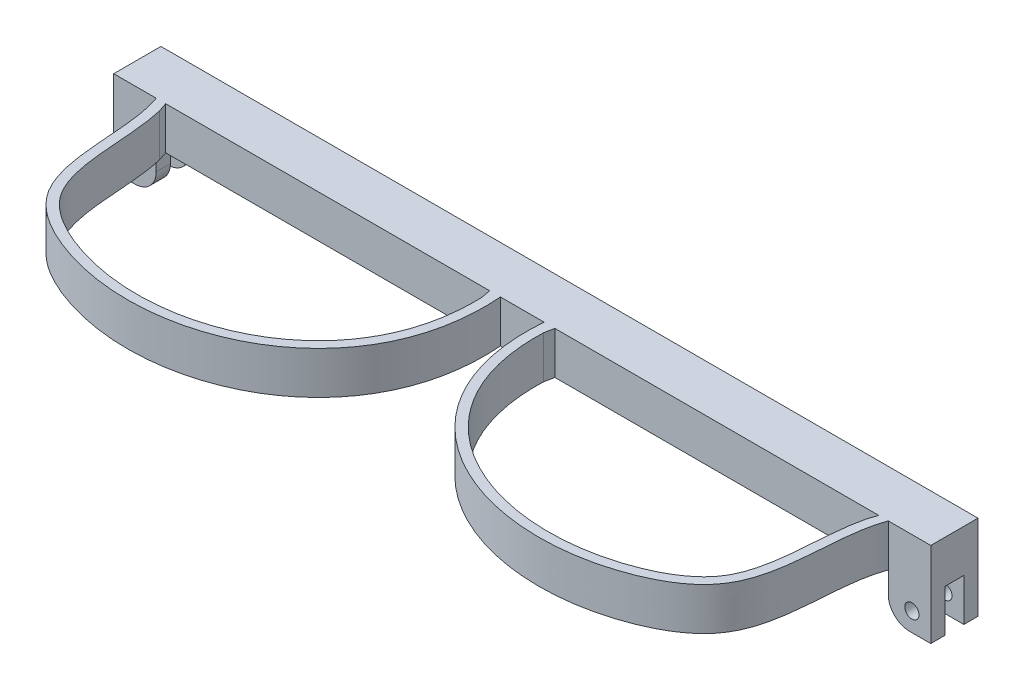
SolidWorks part; units mm, degrees
ref_plane "前视基准面" through (0, 0, 0) normal (0, 0, 1) x (1, 0, 0)
ref_plane "上视基准面" through (0, 0, 0) normal (0, 1, 0) x (1, 0, 0)
ref_plane "右视基准面" through (0, 0, 0) normal (1, 0, 0) x (0, 0, -1)
sketch "草图1" plane through (0, 0, 0) normal (0, 1, 0) x (1, 0, 0)
  line L0 (-85, 29.8187) -> (85, 29.8187)
  line L1 (85, 29.8187) -> (85, -30.1813)
  line L2 (85, -30.1813) -> (-85, -30.1813)
  line L3 (-85, -30.1813) -> (-85, 29.8187)
  line L4 (-77.5, 21.6616) -> (77.5, 21.6616)
  line L5 (-77.5, 21.6616) -> (-77.5, 11.6616)
  line L6 (-77.5, 11.6616) -> (-4.6224, 11.6616)
  line L8 (-74.8263, 9.6616) -> (-6.5113, 9.6616) construction
  line L10 (-4.6224, 11.6616) -> (4.6224, 11.6616)
  line L11 (0, 29.8187) -> (0, -30.1813) construction
  line L12 (77.5, 11.6616) -> (4.6224, 11.6616)
  line L13 (77.5, 21.6616) -> (77.5, 11.6616)
  spline S0 degree 3 poles (-77.5, 11.6616) (-74.4077, 3.1869) (-78.1308, -15.9273) (-40.2589, -37.426) (-2.1163, -20.689) (-4.6224, 11.6616) knots 0 0 0 0 0.246122 0.369792 1 1 1 1
  spline S1 degree 1 poles (-74.8263, 9.6616) (-6.5113, 9.6616) knots 0 0 1 1 construction
  spline S2 degree 3 poles (-74.8263, 9.6616) (-74.5371, 8.4402) (-74.1186, 5.9785) (-73.6218, 0.8691) (-73.2546, -5.557) (-72.241, -11.3706) (-70.6014, -15.2078) (-68.2701, -18.4305) (-63.7315, -21.7629) (-56.8543, -24.5334) (-49.7226, -26.1197) (-40.0582, -26.6566) (-30.6361, -24.878) (-22.3142, -20.9083) (-16.8289, -16.8747) (-12.2912, -11.8166) (-9.4499, -6.76) (-7.8343, -2.2025) (-6.9771, 1.4731) (-6.5812, 4.7599) (-6.4697, 7.5102) (-6.4856, 8.9503) (-6.5113, 9.6616) knots 0.022831 0.022831 0.022831 0.022831 0.052972 0.083113 0.143395 0.203676 0.233817 0.263958 0.324239 0.384521 0.444802 0.505084 0.625647 0.685929 0.74621 0.806492 0.866773 0.896914 0.927055 0.957196 0.972266 0.987337 0.987337 0.987337 0.987337
  spline S3 degree 1 poles (-74.8263, 9.6616) (-75.4985, 11.6616) knots 0 0 1 1
  spline S4 degree 1 poles (-6.5113, 9.6616) (-6.9074, 11.6616) knots 0 0 1 1
  spline S5 degree 1 poles (74.8263, 9.6616) (75.4985, 11.6616) knots 0 0 1 1
  spline S6 degree 1 poles (6.5113, 9.6616) (6.9074, 11.6616) knots 0 0 1 1
  spline S7 degree 3 poles (74.8263, 9.6616) (74.5371, 8.4402) (74.1186, 5.9785) (73.6218, 0.8691) (73.2546, -5.557) (72.241, -11.3706) (70.6014, -15.2078) (68.2701, -18.4305) (63.7315, -21.7629) (56.8543, -24.5334) (49.7226, -26.1197) (40.0582, -26.6566) (30.6361, -24.878) (22.3142, -20.9083) (16.8289, -16.8747) (12.2912, -11.8166) (9.4499, -6.76) (7.8343, -2.2025) (6.9771, 1.4731) (6.5812, 4.7599) (6.4697, 7.5102) (6.4856, 8.9503) (6.5113, 9.6616) knots 0.022831 0.022831 0.022831 0.022831 0.052972 0.083113 0.143395 0.203676 0.233817 0.263958 0.324239 0.384521 0.444802 0.505084 0.625647 0.685929 0.74621 0.806492 0.866773 0.896914 0.927055 0.957196 0.972266 0.987337 0.987337 0.987337 0.987337
  spline S8 degree 3 poles (77.5, 11.6616) (74.4077, 3.1869) (78.1308, -15.9273) (40.2589, -37.426) (2.1163, -20.689) (4.6224, 11.6616) knots 0 0 0 0 0.246122 0.369792 1 1 1 1
  point P3 (0, 29.8187)
  point P25 (0, 11.6616)
  point P31 (0, 21.6616)
  dimension "D1" = 60
  dimension "D2" = 170
  dimension "D3" = 10
  dimension "D4" = 77.5
  dimension "D5" = 2
extrude "frame_前端" add sketch "草图1" along normal blind 9 contours L13 L4 L5 L6 L10 L12 | S8 L12 S5 S7 S6 | S4 S2 S3 L6 S0 region at (0, 0, -16.6616) region at (-76.4992, 0, -10.8291) region at (42.3457, 0, 27.4934)
sketch "frame前端线槽草图" plane through (77.5, 0, 0) normal (1, 0, 0) x (0, 0, -1)
  line L0 (11.6616, 9) -> (11.6616, 0)
  line L2 (21.6616, 0) -> (21.6616, 9)
  line L3 (21.6616, 9) -> (11.6616, 9)
  line L4 (11.6616, 9) -> (21.6616, 0) construction
  line L5 (11.6616, 0) -> (21.6616, 9) construction
  line L6 (11.6616, 0) -> (13.6616, 0)
  line L7 (13.6616, 0) -> (13.6616, 7.2)
  line L8 (13.6616, 7.2) -> (19.6616, 7.2)
  line L9 (19.6616, 7.2) -> (19.6616, 0)
  line L10 (19.6616, 0) -> (21.6616, 0)
  line L11 (13.6616, 0) -> (19.6616, 0)
  line L12 (11.6616, 9) -> (11.6616, 0)
  line L13 (13.6616, 0) -> (13.6616, 7.2)
  line L14 (19.6616, 7.2) -> (19.6616, 0)
  line L15 (21.6616, 0) -> (21.6616, 9)
  point P4 (16.6616, 4.5)
  point P24 (16.6616, 4.5)
  dimension "D1" = 2
ref_plane "左侧connection草图生成面" through (0, 0, -16.6616) normal (0, 0, -1) x (-1, 0, 0)
ref_plane "向中间生成connection基底的基准面左" through (86.5, 0, 0) normal (1, 0, 0) x (0, 0, -1)
sketch "草图5" plane through (86.5, 0, 0) normal (1, 0, 0) x (0, 0, -1)
  line L0 (11.6616, 9) -> (11.6616, 0)
  line L1 (11.6616, 0) -> (21.6616, 0)
  line L2 (21.6616, 0) -> (21.6616, 9)
  line L3 (21.6616, 9) -> (11.6616, 9)
extrude "向中间生成connection的基底左" add sketch "草图5" against normal blind 9
sketch "草图9" plane through (0, 0, -16.6616) normal (0, 0, -1) x (-1, 0, 0)
  line L1 (-86.5, 4.95) -> (-86.5, -4.95) construction
  line L4 (-86.5, 0) -> (-86.5, -9)
  line L5 (-86.5, -9) -> (-82, -9)
  line L7 (-86.5, 0) -> (-77.5, 0)
  line L8 (77.5, 0) -> (-86.5, 0) construction
  line L9 (-77.5, 0) -> (-77.5, -4.5)
  arc A2 (-82, -9) -> (-77.5, -4.5) centre (-82, -4.5) ccw
  dimension "D4" = 9
  dimension "D1" = 9
  dimension "D2" = 4.5
  dimension "D3" = 4.5
extrude "生成connection左上" add sketch "草图9" along normal blind 5
extrude "生成connection左下" add sketch "草图9<3>" against normal blind 5
sketch "草图9<3>" plane through (0, 0, -16.6616) normal (0, 0, -1) x (-1, 0, 0) same geometry as "草图9"
extrude "生成connection口左上" cut sketch "草图9<4>" against normal blind 2
sketch "草图9<4>" plane through (0, 0, -16.6616) normal (0, 0, -1) x (-1, 0, 0) same geometry as "草图9"
extrude "生成connection口左下" cut sketch "草图9<6>" along normal blind 2
sketch "草图9<6>" plane through (0, 0, -16.6616) normal (0, 0, -1) x (-1, 0, 0) same geometry as "草图9"
ref_plane "线槽口草图基准面" through (77.5, 0, 0) normal (1, 0, 0) x (0, 0, -1)
sketch "线槽口草图" plane through (77.5, 0, 0) normal (1, 0, 0) x (0, 0, -1)
  line L3 (19.6616, 0) -> (19.6616, 7.2)
  line L4 (19.6616, 7.2) -> (13.6616, 7.2)
  line L5 (13.6616, 7.2) -> (13.6616, 0)
  line L8 (13.6616, 0) -> (19.6616, 0)
extrude "挖槽" cut sketch "线槽口草图" against normal blind 155
ref_plane "向中间生成connection基底的基准面右" through (-86.5, 0, 0) normal (-1, 0, 0) x (0, 0, 1)
sketch "草图12" plane through (-86.5, 0, 0) normal (-1, 0, 0) x (0, 0, 1)
  line L0 (-21.6616, 9) -> (-11.6616, 9)
  line L1 (-11.6616, 9) -> (-11.6616, 0)
  line L2 (-11.6616, 0) -> (-21.6616, 0)
  line L3 (-21.6616, 0) -> (-21.6616, 9)
extrude "向中间生成connection的基底右" add sketch "草图12" against normal blind 9
ref_plane "右侧connection草图生成面" through (0, 0, -16.6616) normal (0, 0, -1) x (-1, 0, 0)
sketch "草图13" plane through (0, 0, -16.6616) normal (0, 0, -1) x (-1, 0, 0)
  line L2 (86.5, 0) -> (77.5, 0)
  line L3 (86.5, 0) -> (-77.5, 0) construction
  line L4 (86.5, -55) -> (86.5, 55) construction
  line L5 (86.5, 0) -> (86.5, -9)
  line L6 (77.5, 0) -> (77.5, -4.5)
  line L7 (82, -9) -> (86.5, -9)
  arc A2 (77.5, -4.5) -> (82, -9) centre (82, -4.5) ccw
  dimension "D3" = 4.5
  dimension "D1" = 9
  dimension "D2" = 9
extrude "生成connection右上" add sketch "草图13" along normal blind 5
extrude "生成connection右下" add sketch "草图13<2>" against normal blind 5
sketch "草图13<2>" plane through (0, 0, -16.6616) normal (0, 0, -1) x (-1, 0, 0) same geometry as "草图13"
extrude "生成connection口右上" cut sketch "草图13<3>" against normal blind 2
sketch "草图13<3>" plane through (0, 0, -16.6616) normal (0, 0, -1) x (-1, 0, 0) same geometry as "草图13"
extrude "生成connection口右下" cut sketch "草图13<4>" along normal blind 2
sketch "草图13<4>" plane through (0, 0, -16.6616) normal (0, 0, -1) x (-1, 0, 0) same geometry as "草图13"
sketch "孔" plane through (0, 0, -21.6616) normal (0, 0, -1) x (-1, 0, 0)
  line L6 (-86.5, 9) -> (-86.5, -9)
  line L8 (-77.5, 0) -> (77.5, 0)
  line L9 (77.5, 0) -> (77.5, -4.5)
  line L10 (82, -9) -> (86.5, -9)
  line L11 (86.5, -9) -> (86.5, 9)
  line L12 (86.5, 9) -> (-86.5, 9)
  line L15 (-86.5, 9) -> (-86.5, -9)
  line L16 (-77.5, 0) -> (77.5, 0)
  line L18 (82, -9) -> (86.5, -9)
  line L19 (86.5, -9) -> (86.5, 9)
  line L20 (86.5, 9) -> (-86.5, 9)
  line L24 (-86.5, -9) -> (-82, -9)
  line L25 (-86.5, -9) -> (-82, -9)
  line L26 (-77.5, -4.5) -> (-77.5, 0)
  line L27 (-77.5, -4.5) -> (-77.5, 0)
  line L29 (77.5, 0) -> (77.5, -4.5)
  circle A0 centre (-82.5, -5) radius 1.5
  circle A1 centre (82, -4.5) radius 1.9354
  arc A2 (77.5, -4.5) -> (82, -9) centre (82, -4.5) ccw
  arc A4 (77.5, -4.5) -> (82, -9) centre (82, -4.5) ccw
  arc A7 (-82, -9) -> (-77.5, -4.5) centre (-82, -4.5) ccw
  arc A8 (-82, -9) -> (-77.5, -4.5) centre (-82, -4.5) ccw
  dimension "D2" = 3
  dimension "D1" = 0
extrude "打孔" cut sketch "孔" against normal through all flip side to cut
